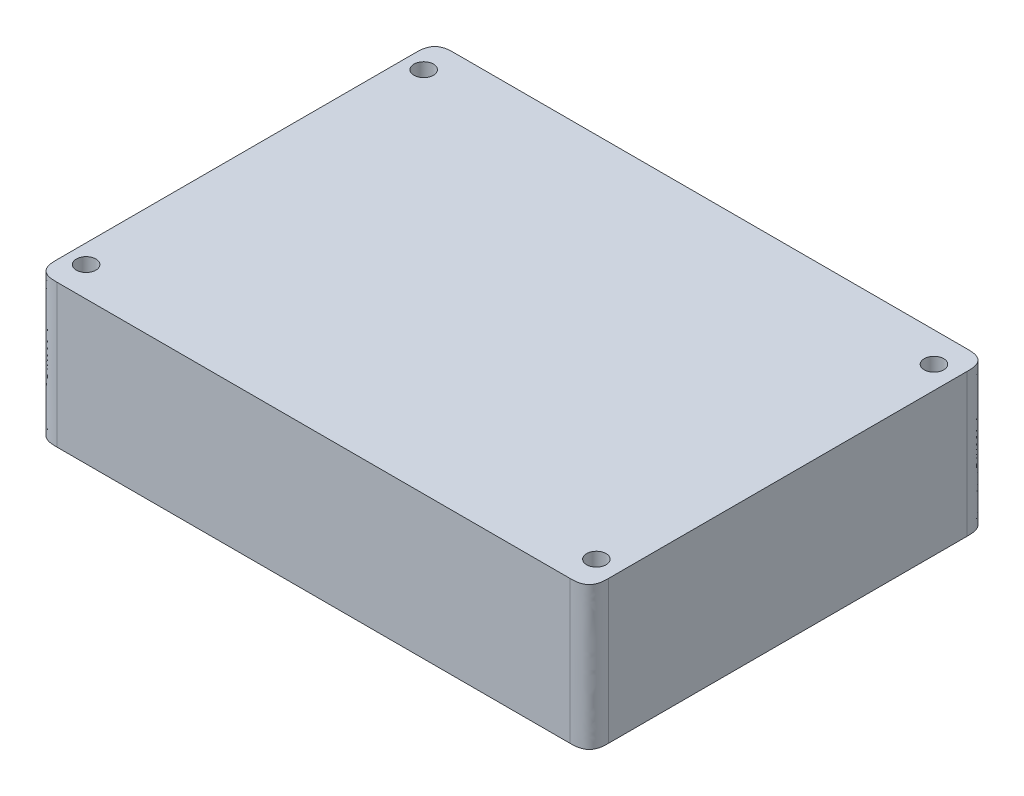
SolidWorks part; units mm, degrees
material "自定义塑料"
ref_plane "前视基准面" through (0, 0, 0) normal (0, 0, 1) x (1, 0, 0)
ref_plane "上视基准面" through (0, 0, 0) normal (0, 1, 0) x (1, 0, 0)
ref_plane "右视基准面" through (0, 0, 0) normal (1, 0, 0) x (0, 0, -1)
other "Configuration Table"
sketch "草图1" plane through (0, 0, 0) normal (0, 1, 0) x (1, 0, 0)
  line L0 (-51.353, 30.8481) -> (-51.353, -47.0578) construction
  line L1 (-54.253, 26.2168) -> (30.747, 26.2168)
  line L2 (-54.253, 26.2168) -> (-54.253, -34.9832)
  line L3 (-54.253, -34.9832) -> (30.747, -34.9832)
  line L4 (30.747, 26.2168) -> (30.747, -34.9832)
  line L5 (-60.5384, 21.6168) -> (41.8476, 21.6168) construction
  line L6 (27.247, 29.6903) -> (27.247, -45.5692) construction
  line L7 (-60.5384, -30.3832) -> (59.8768, -30.3832) construction
  circle A0 centre (-51.353, 21.6168) radius 1.5
  circle A1 centre (-51.353, -30.3832) radius 1.5
  circle A2 centre (27.247, 21.6168) radius 1.5
  circle A3 centre (27.247, -30.3832) radius 1.5
  dimension "D1" = 61.2
  dimension "D2" = 85
  dimension "D3" = 4.6
  dimension "D4" = 52
  dimension "D5" = 2.9
  dimension "D6" = 78.6
extrude "凸台-拉伸1" add sketch "草图1" along normal blind 22
fillet "圆角1" radius 3 4 edges at (-54.253, 11, -26.2168) (30.747, 11, -26.2168) (-54.253, 11, 34.9832) (30.747, 11, 34.9832) curvature continuous yes
